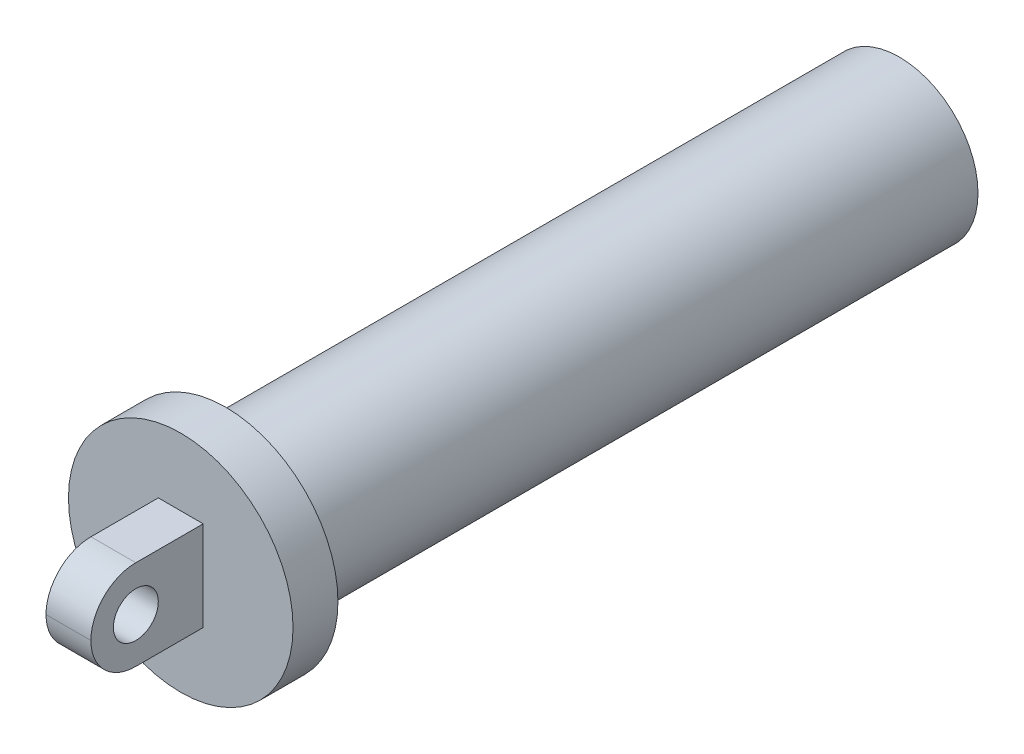
SolidWorks part; units mm, degrees
ref_plane "Front Plane" through (0, 0, 0) normal (0, 0, 1) x (1, 0, 0)
ref_plane "Top Plane" through (0, 0, 0) normal (0, 1, 0) x (1, 0, 0)
ref_plane "Right Plane" through (0, 0, 0) normal (1, 0, 0) x (0, 0, -1)
sketch "Sketch2" plane through (0, 0, 0) normal (0, 0, 1) x (1, 0, 0)
  circle A0 centre (0, 0) radius 25
  dimension "1" = 50
extrude "Boss-Extrude2" add sketch "Sketch2" along normal blind 10
sketch "Sketch3" plane through (0, 0, 10) normal (0, 0, 1) x (1, 0, 0)
  line L1 (-5, 10) -> (5, 10)
  line L2 (-5, 10) -> (-5, -10)
  line L3 (-5, -10) -> (5, -10)
  line L4 (5, 10) -> (5, -10)
  line L5 (-5, 10) -> (5, -10) construction
  line L6 (-5, -10) -> (5, 10) construction
  point P0 (0, 0)
  dimension "D1" = 20
  dimension "D2" = 10
extrude "Boss-Extrude3" add sketch "Sketch3" along normal blind 25
sketch "Sketch4" plane through (-5, 0, 0) normal (-1, 0, 0) x (0, 0, 1)
  line L0 (35, 10) -> (35, -10) construction
  line L1 (35, -10) -> (10, -10) construction
  circle A0 centre (25, 0) radius 5
  dimension "D1" = 10
  dimension "D2" = 10
  dimension "D3" = 10
extrude "Cut-Extrude1" cut sketch "Sketch4" against normal blind 20
fillet "Fillet1" radius 10 2 edges at (0, -10, 35) (0, 10, 35)
sketch "Sketch5" plane through (0, 0, 0) normal (0, 0, -1) x (-1, 0, 0)
  circle A0 centre (0, 0) radius 12.5
  circle A1 centre (0, 0) radius 17.5
extrude "Boss-Extrude4" add sketch "Sketch5" along normal blind 150
